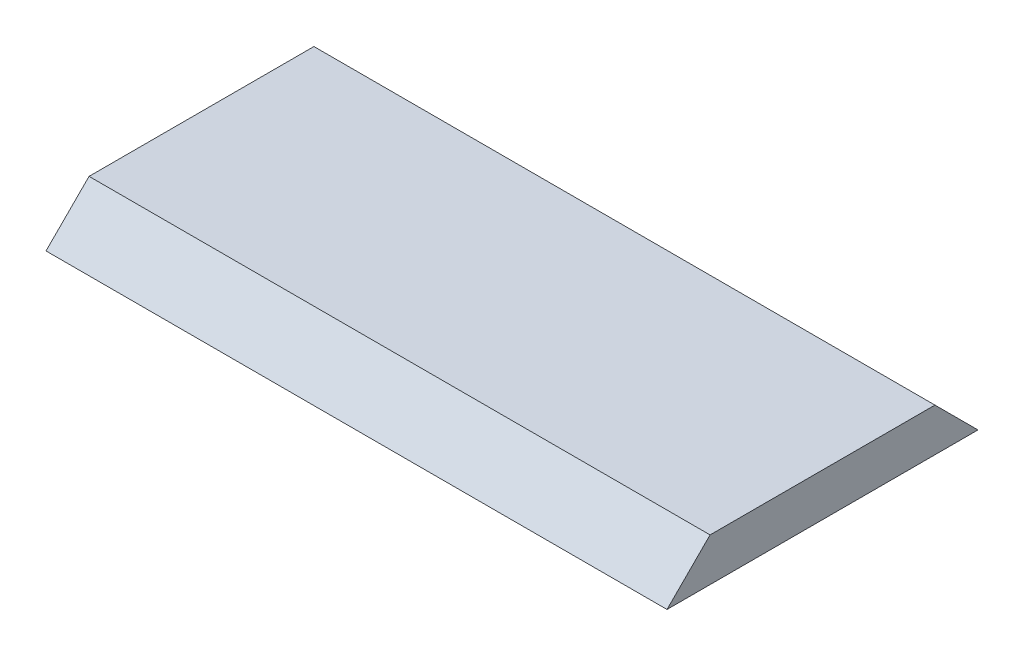
SolidWorks part; units mm, degrees
material "ABS"
ref_plane "Front Plane" through (0, 0, 0) normal (0, 0, 1) x (1, 0, 0)
ref_plane "Top Plane" through (0, 0, 0) normal (0, 1, 0) x (1, 0, 0)
ref_plane "Right Plane" through (0, 0, 0) normal (1, 0, 0) x (0, 0, -1)
sketch "Sketch1" plane through (0, 0, 0) normal (0, 1, 0) x (1, 0, 0)
  line L1 (-64.9, 32.5) -> (64.9, 32.5)
  line L2 (-64.9, 32.5) -> (-64.9, -32.5)
  line L3 (-64.9, -32.5) -> (64.9, -32.5)
  line L4 (64.9, 32.5) -> (64.9, -32.5)
  line L5 (-64.9, 32.5) -> (64.9, -32.5) construction
  line L6 (-64.9, -32.5) -> (64.9, 32.5) construction
  point P0 (0, 0)
  dimension "D1" = 129.8
  dimension "D2" = 65
extrude "Boss-Extrude1" add sketch "Sketch1" along normal blind 9
sketch "Sketch2" plane through (0, 0, 0) normal (0, -1, 0) x (1, 0, 0)
  line L0 (-64.9, 0) -> (64.9, 0) construction
  line L1 (-64.9, -32.5) -> (-64.9, 32.5) construction
  line L2 (64.9, 32.5) -> (64.9, -32.5) construction
  line L4 (-32.45, 20) -> (0, 20) construction
  line L5 (-64.9, 20) -> (-32.45, 20) construction
  line L6 (0, 20) -> (32.45, 20) construction
  line L7 (32.45, 20) -> (64.9, 20) construction
  circle A0 centre (-32.45, 20) radius 2.35
  circle A1 centre (0, 20) radius 2.35
  circle A2 centre (32.45, 20) radius 2.35
  circle A3 centre (32.45, -20) radius 2.35
  circle A4 centre (0, -20) radius 2.35
  circle A5 centre (-32.45, -20) radius 2.35
  point P22 (-64.9, 16.25)
  dimension "D1" = 4.7
  dimension "D2" = 4.7
  dimension "D3" = 4.7
  dimension "D4" = 20
extrude "Cut-Extrude1" cut sketch "Sketch2" against normal blind 8
chamfer "Chamfer1" distance 1 angle 45 6 edges at (-32.45, 0, -17.65) (0, 0, -17.65) (32.45, 0, -17.65) (32.45, 0, 17.65) (0, 0, 17.65) (-32.45, 0, 17.65)
chamfer "Chamfer2" distance 9 angle 45 2 edges at (0, 9, 32.5) (0, 9, -32.5)
